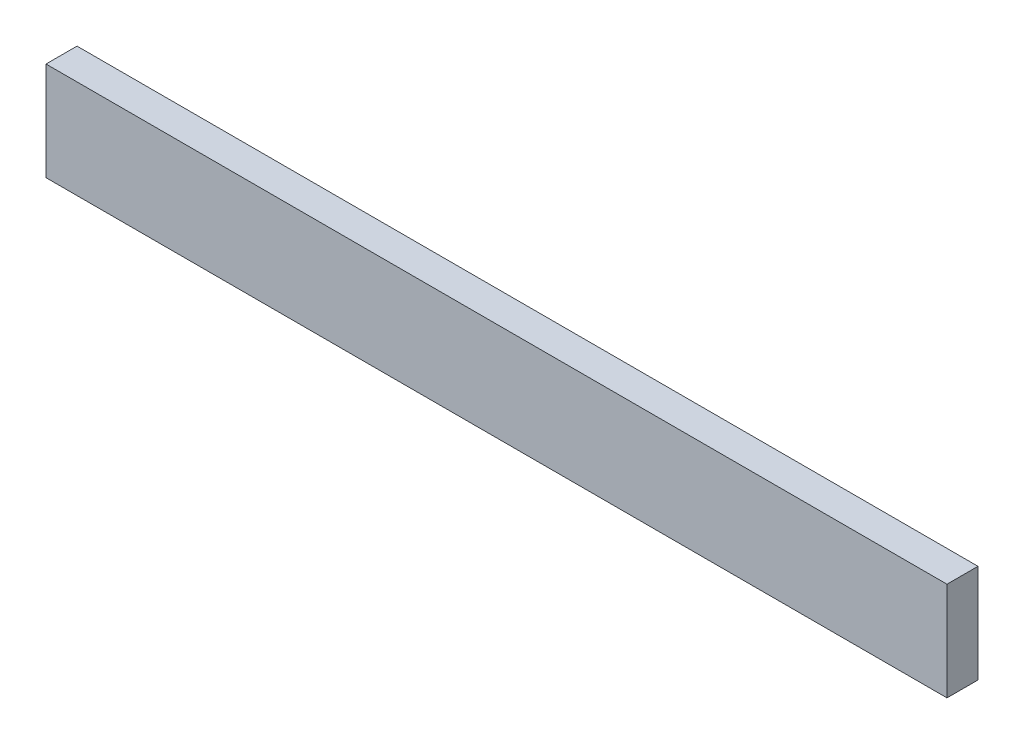
SolidWorks part; units mm, degrees
ref_plane "Front Plane" through (0, 0, 0) normal (0, 0, 1) x (1, 0, 0)
ref_plane "Top Plane" through (0, 0, 0) normal (0, 1, 0) x (1, 0, 0)
ref_plane "Right Plane" through (0, 0, 0) normal (1, 0, 0) x (0, 0, -1)
sketch "Sketch1" plane through (0, 0, 0) normal (0, 0, 1) x (1, 0, 0)
  line L1 (-23.241, -2.54) -> (23.241, -2.54)
  line L2 (-23.241, -2.54) -> (-23.241, 2.54)
  line L3 (-23.241, 2.54) -> (23.241, 2.54)
  line L4 (23.241, -2.54) -> (23.241, 2.54)
  line L5 (-23.241, -2.54) -> (23.241, 2.54) construction
  line L6 (-23.241, 2.54) -> (23.241, -2.54) construction
  point P0 (0, 0)
  dimension "D1" = 46.482
  dimension "D2" = 5.08
extrude "Boss-Extrude1" add sketch "Sketch1" along normal blind 1.6
